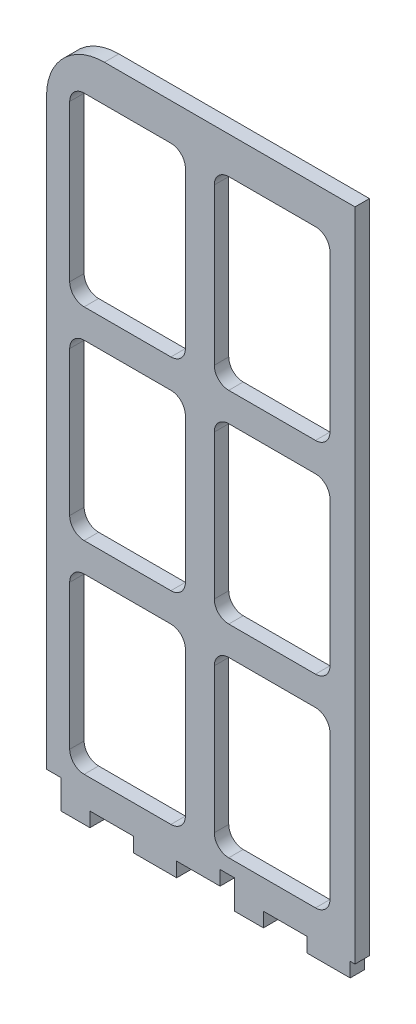
SolidWorks part; units mm, degrees
material "Balsa"
ref_plane "Front Plane" through (0, 0, 0) normal (0, 0, 1) x (1, 0, 0)
ref_plane "Top Plane" through (0, 0, 0) normal (0, 1, 0) x (1, 0, 0)
ref_plane "Right Plane" through (0, 0, 0) normal (1, 0, 0) x (0, 0, -1)
sketch "Sketch1" plane through (0, 0, 0) normal (0, 0, 1) x (1, 0, 0)
  line L1 (135.4577, 0) -> (135.4577, 287.9852)
  line L2 (135.4577, 287.9852) -> (25.4, 287.9852)
  line L4 (0, 0) -> (0, -6.35)
  line L6 (0, 0) -> (0, -6.35)
  line L7 (0, -6.35) -> (19.05, -6.35)
  line L8 (19.05, 0) -> (19.05, -6.35)
  line L10 (38.1, 0) -> (38.1, -6.35)
  line L11 (38.1, -6.35) -> (57.15, -6.35)
  line L12 (57.15, 0) -> (57.15, -6.35)
  line L14 (76.2, 0) -> (76.2, -6.35)
  line L15 (76.2, -6.35) -> (95.25, -6.35)
  line L16 (95.25, 0) -> (95.25, -6.35)
  line L18 (114.3, 0) -> (114.3, -6.35)
  line L19 (114.3, -6.35) -> (133.35, -6.35)
  line L20 (133.35, 0) -> (133.35, -6.35)
  line L25 (19.05, 0) -> (38.1, 0)
  line L26 (57.15, 0) -> (76.2, 0)
  line L27 (95.25, 0) -> (114.3, 0)
  line L28 (133.35, 0) -> (135.4577, 0)
  line L30 (0, 262.5852) -> (0, 0)
  line L31 (25.4, 287.9852) -> (135.4577, 287.9852)
  line L32 (19.05, 0) -> (38.1, 0)
  line L33 (38.1, -6.35) -> (57.15, -6.35)
  line L34 (57.15, 0) -> (76.2, 0)
  arc A0 (25.4, 287.9852) -> (0, 262.5852) centre (25.4, 262.5852) ccw
  point P8 (0, 287.9852)
  point P11 (135.4577, 287.9852)
  dimension "D4" = 6.35
  dimension "D5" = 19.05
  dimension "D1" = 135.4577
  dimension "D2" = 287.9852
  dimension "D3" = 135.4577
  dimension "D6" = 6.35
  dimension "D7" = 19.05
  dimension "D8" = 19.05
  dimension "D9" = 19.05
  dimension "D10" = 19.05
  dimension "D11" = 6.35
  dimension "D12" = 19.05
  dimension "D13" = 19.05
  dimension "D14" = 6.35
  dimension "D15" = 6.35
  dimension "D16" = 0
  dimension "D17" = 262.5852
  dimension "D21" = 6.35
  dimension "D22" = 6.35
  dimension "D23" = 6.35
extrude "Boss-Extrude1" add sketch "Sketch1" along normal blind 6.35 contours L2 A0 L30 L4 L7 L8 L25 L10 L11 L12 L26 L14 L15 L16 L27 L18 L19 L20 L1 region at (67.9342, 141.6966, 0)
sketch "Sketch2" plane through (0, 0, 6.35) normal (0, 0, 1) x (1, 0, 0)
  line L38 (73.66, 19.05) -> (73.66, 82.55)
  line L39 (16.51, 12.7) -> (54.61, 12.7)
  line L40 (73.66, 196.85) -> (73.66, 265.43)
  line L41 (80.01, 190.5) -> (118.11, 190.5)
  line L42 (124.46, 196.85) -> (124.46, 265.43)
  line L43 (80.01, 271.78) -> (118.11, 271.78)
  line L45 (10.16, 196.85) -> (10.16, 265.43)
  line L46 (16.51, 190.5) -> (54.61, 190.5)
  line L47 (60.96, 196.85) -> (60.96, 265.43)
  line L48 (16.51, 271.78) -> (54.61, 271.78)
  line L49 (73.66, 107.95) -> (73.66, 171.45)
  line L50 (80.01, 101.6) -> (118.11, 101.6)
  line L51 (124.46, 107.95) -> (124.46, 171.45)
  line L52 (80.01, 177.8) -> (118.11, 177.8)
  line L53 (10.16, 107.95) -> (10.16, 171.45)
  line L54 (16.51, 101.6) -> (54.61, 101.6)
  line L55 (60.96, 107.95) -> (60.96, 171.45)
  line L56 (16.51, 177.8) -> (54.61, 177.8)
  line L68 (10.16, 19.05) -> (10.16, 82.55)
  line L69 (16.51, 88.9) -> (54.61, 88.9)
  line L70 (60.96, 19.05) -> (60.96, 82.55)
  line L71 (80.01, 12.7) -> (118.11, 12.7)
  line L72 (124.46, 19.05) -> (124.46, 82.55)
  line L73 (80.01, 88.9) -> (118.11, 88.9)
  line L104 (19.05, -38.1) -> (44.45, -38.1) [skipped]
  line L105 (137.16, 19.05) -> (137.16, 82.55) [skipped]
  line L106 (146.05, 12.7) -> (171.45, 12.7) [skipped]
  line L107 (187.96, 19.05) -> (187.96, 82.55) [skipped]
  line L108 (146.05, 88.9) -> (171.45, 88.9) [skipped]
  line L109 (137.16, -44.45) -> (137.16, 19.05) [skipped]
  line L110 (146.05, -50.8) -> (171.45, -50.8) [skipped]
  line L111 (187.96, -44.45) -> (187.96, 19.05) [skipped]
  line L112 (146.05, 25.4) -> (171.45, 25.4) [skipped]
  line L113 (137.16, -103.373) -> (137.16, -49.027) [skipped]
  line L114 (150.627, -114.3) -> (166.873, -114.3) [skipped]
  line L115 (187.96, -103.373) -> (187.96, -49.027) [skipped]
  line L116 (150.627, -38.1) -> (166.873, -38.1) [skipped]
  line L117 (73.66, -97.4702) -> (73.66, -54.9298) [skipped]
  line L118 (124.46, -97.4702) -> (124.46, -54.9298) [skipped]
  line L119 (93.0298, -114.3) -> (97.4702, -114.3) [skipped]
  line L120 (93.0298, -38.1) -> (97.4702, -38.1) [skipped]
  line L121 (10.16, -105.3232) -> (10.16, -47.0768) [skipped]
  line L122 (37.2067, -114.3) -> (48.1202, -114.3) [skipped]
  line L123 (60.96, -105.3232) -> (60.96, -58.7589) [skipped]
  line L124 (19.05, 25.4) -> (44.45, 25.4) [skipped]
  line L125 (60.96, -50.8) -> (60.96, 25.4) [skipped]
  line L126 (19.05, -50.8) -> (44.45, -50.8) [skipped]
  line L127 (10.16, -50.8) -> (10.16, 25.4) [skipped]
  line L128 (124.46, -69.3053) -> (124.46, 6.8947) [skipped]
  line L129 (73.66, -50.8) -> (73.66, 25.4) [skipped]
  line L130 (94.7053, 25.4) -> (103.4599, 25.4) [skipped]
  line L131 (94.7053, -50.8) -> (103.4599, -50.8) [skipped]
  arc A24 (73.66, 82.55) -> (80.01, 88.9) centre (80.01, 82.55) cw
  arc A25 (124.46, 82.55) -> (118.11, 88.9) centre (118.11, 82.55) ccw
  arc A26 (118.11, 12.7) -> (124.46, 19.05) centre (118.11, 19.05) ccw
  arc A27 (73.66, 19.05) -> (80.01, 12.7) centre (80.01, 19.05) ccw
  arc A28 (54.61, 12.7) -> (60.96, 19.05) centre (54.61, 19.05) ccw
  arc A29 (54.61, 88.9) -> (60.96, 82.55) centre (54.61, 82.55) cw
  arc A30 (10.16, 82.55) -> (16.51, 88.9) centre (16.51, 82.55) cw
  arc A31 (16.51, 12.7) -> (10.16, 19.05) centre (16.51, 19.05) cw
  arc A57 (10.16, 196.85) -> (16.51, 190.5) centre (16.51, 196.85) ccw
  arc A58 (10.16, 265.43) -> (16.51, 271.78) centre (16.51, 265.43) cw
  arc A59 (60.96, 265.43) -> (54.61, 271.78) centre (54.61, 265.43) ccw
  arc A60 (54.61, 190.5) -> (60.96, 196.85) centre (54.61, 196.85) ccw
  arc A61 (73.66, 196.85) -> (80.01, 190.5) centre (80.01, 196.85) ccw
  arc A62 (73.66, 265.43) -> (80.01, 271.78) centre (80.01, 265.43) cw
  arc A63 (124.46, 265.43) -> (118.11, 271.78) centre (118.11, 265.43) ccw
  arc A64 (118.11, 190.5) -> (124.46, 196.85) centre (118.11, 196.85) ccw
  arc A65 (10.16, 107.95) -> (16.51, 101.6) centre (16.51, 107.95) ccw
  arc A66 (10.16, 171.45) -> (16.51, 177.8) centre (16.51, 171.45) cw
  arc A67 (60.96, 171.45) -> (54.61, 177.8) centre (54.61, 171.45) ccw
  arc A68 (54.61, 101.6) -> (60.96, 107.95) centre (54.61, 107.95) ccw
  arc A69 (73.66, 107.95) -> (80.01, 101.6) centre (80.01, 107.95) ccw
  arc A70 (73.66, 171.45) -> (80.01, 177.8) centre (80.01, 171.45) cw
  arc A71 (124.46, 171.45) -> (118.11, 177.8) centre (118.11, 171.45) ccw
  arc A72 (118.11, 101.6) -> (124.46, 107.95) centre (118.11, 107.95) ccw
  point P88 (60.96, 12.7)
  point P93 (10.16, 88.9)
  point P96 (10.16, 12.7)
  dimension "D7" = 81.28
  dimension "D12" = 76.2
  dimension "D11" = 50.8
  dimension "D1" = 76.2
  dimension "D2" = 50.8
  dimension "D3" = 3
  dimension "D4" = 3
  dimension "D5" = 10.16
  dimension "D6" = 12.7
  dimension "D8" = 12.7
  dimension "D9" = 81.28
  dimension "D10" = 50.8
  dimension "D13" = 76.2
  dimension "D14" = 50.8
  dimension "D15" = 50.8
  dimension "D16" = 12.7
  dimension "D17" = 12.7
  dimension "D18" = 0
  dimension "D19" = 0
  dimension "D20" = 12.7
  dimension "D21" = 12.7
  dimension "D22" = 12.7
  dimension "D23" = 12.7
extrude "Cut-Extrude1" cut sketch "Sketch2" against normal through all
sketch "Sketch3" plane through (0, 0, 6.35) normal (0, 0, 1) x (1, 0, 0)
  line L1 (0, -6.35) -> (6.35, -6.35)
  line L2 (0, -6.35) -> (0, 6.35)
  line L3 (0, 6.35) -> (6.35, 6.35)
  line L4 (6.35, -6.35) -> (6.35, 6.35)
  line L5 (76.2, -6.35) -> (82.55, -6.35)
  line L6 (76.2, -6.35) -> (76.2, 6.35)
  line L7 (76.2, 6.35) -> (82.55, 6.35)
  line L8 (82.55, -6.35) -> (82.55, 6.35)
  dimension "D1" = 6.35
  dimension "D2" = 12.7
  dimension "D3" = 6.35
  dimension "D4" = 12.7
extrude "Cut-Extrude2" cut sketch "Sketch3" against normal through all
